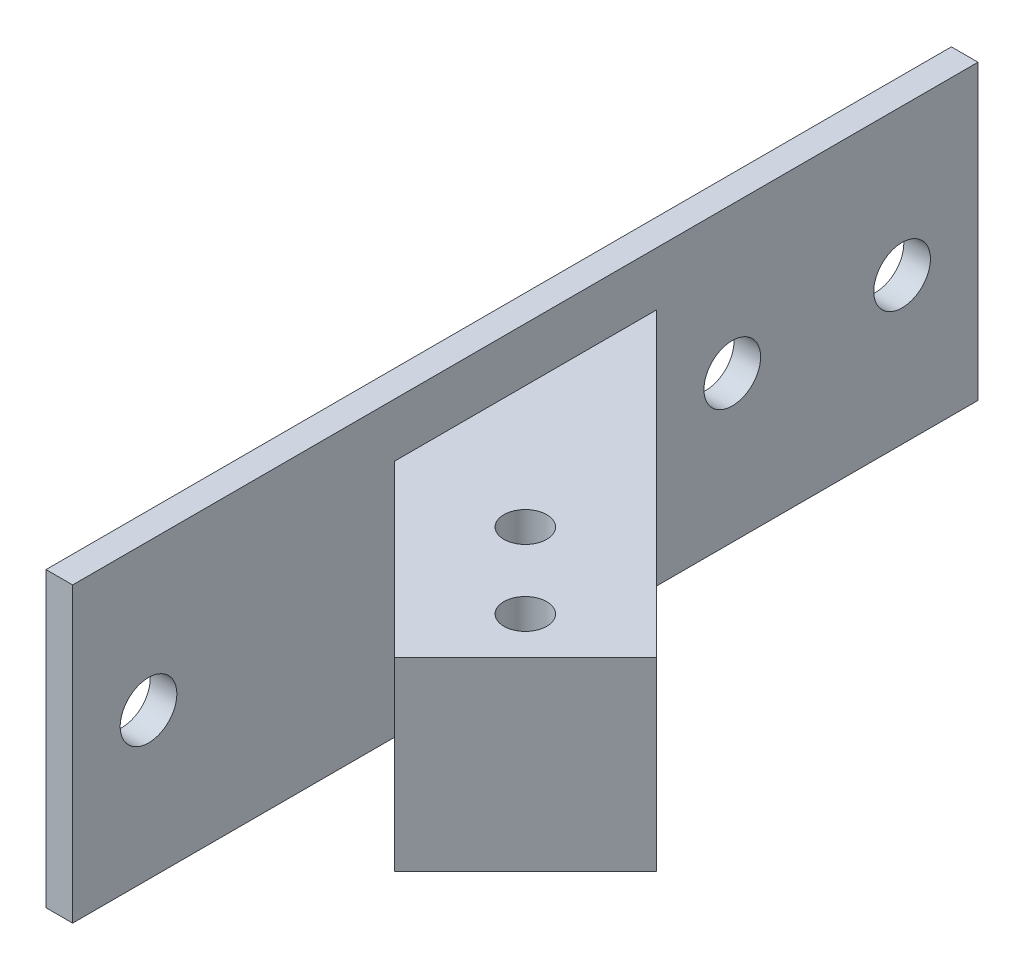
SolidWorks part; units mm, degrees
material "6061 Alloy"
ref_plane "Front" through (0, 0, 0) normal (0, 0, 1) x (1, 0, 0)
ref_plane "Top" through (0, 0, 0) normal (0, 1, 0) x (1, 0, 0)
ref_plane "Right" through (0, 0, 0) normal (1, 0, 0) x (0, 0, -1)
sketch "Sketch1" plane through (0, 0, 0) normal (1, 0, 0) x (0, 0, -1)
  line L1 (-53.975, 17.4625) -> (53.975, 17.4625)
  line L2 (-53.975, 17.4625) -> (-53.975, -17.4625)
  line L3 (-53.975, -17.4625) -> (53.975, -17.4625)
  line L4 (53.975, 17.4625) -> (53.975, -17.4625)
  line L5 (-53.975, 17.4625) -> (53.975, -17.4625) construction
  line L6 (-53.975, -17.4625) -> (53.975, 17.4625) construction
  point P0 (0, 0)
  dimension "D1" = 34.925
  dimension "D2" = 107.95
extrude "Boss-Extrude1" add sketch "Sketch1" along normal blind 3.175
sketch "Sketch3" plane through (0, 17.4625, 0) normal (0, 1, 0) x (1, 0, 0)
  line L0 (3.175, 0) -> (31.2383, -28.0633)
  line L1 (3.175, 53.975) -> (3.175, -53.975) construction
  line L2 (3.175, -20.2056) -> (21.1355, -38.1661)
  line L3 (3.175, 20.2056) -> (41.3411, -17.9605)
  line L4 (-3.9803, -13.0503) -> (21.1355, -38.1661) construction
  line L5 (16.2253, 7.1553) -> (41.3411, -17.9605) construction
  line L6 (6.1225, -2.9475) -> (31.2383, -28.0633) construction
  line L7 (21.1355, -38.1661) -> (31.2383, -28.0633)
  point P8 (21.1355, -17.9605)
  point P10 (28.5915, -25.4165)
  dimension "D1" = 14.2875
  dimension "D3" = 45
  dimension "D4" = 25.4
  dimension "D2" = 14.2875
sketch3d "3DSketch1"
  line L0 (3.175, 17.4625, 0) -> (31.2383, 17.4625, 28.0633) construction
sketch "Sketch4" plane through (29.6508, 0, 29.6508) normal (0.7071, 0, 0.7071) x (0.7071, 0, -0.7071)
  line L0 (2.2451, 17.4625) -> (2.2451, -17.4625) construction
  line L1 (-8.8039, -11.049) -> (13.2941, -11.049)
  line L2 (-8.8039, -11.049) -> (-8.8039, 11.049)
  line L3 (-8.8039, 11.049) -> (13.2941, 11.049)
  line L4 (13.2941, -11.049) -> (13.2941, 11.049)
  line L5 (-8.8039, -11.049) -> (13.2941, 11.049) construction
  line L6 (-8.8039, 11.049) -> (13.2941, -11.049) construction
  line L7 (40.4112, 17.4625) -> (-35.921, 17.4625) construction
  line L8 (-35.921, -17.4625) -> (40.4112, -17.4625) construction
  line L14 (-7.2164, 9.4615) -> (18.1836, -15.9385) construction
  line L15 (-10.4549, -12.7) -> (14.9451, 12.7) construction
  point P0 (2.2451, 0)
  point P12 (2.2451, 0)
  point P13 (2.2451, 0)
  dimension "D1" = 22.098
extrude "Boss-Extrude2" add sketch "Sketch4" against normal up to surface (28.6385 mm away) up to face at (3.175, 0, 0)
sketch "Sketch5" plane through (3.175, 0, 0) normal (1, 0, 0) x (0, 0, -1)
  line L0 (15.6256, 0) -> (24.6751, 0) construction
  line L1 (-53.975, 17.4625) -> (-53.975, -17.4625) construction
  line L2 (-44.9256, 0) -> (-53.975, 0) construction
  line L3 (-53.975, 0) -> (-35.8761, 0) construction
  line L4 (-35.8761, 11.049) -> (-35.8761, -11.049) construction
  line L5 (15.6256, 11.049) -> (15.6256, -11.049) construction
  line L6 (24.6751, 0) -> (44.9256, 0) construction
  line L7 (44.9256, 0) -> (53.975, 0) construction
  line L8 (53.975, -17.4625) -> (53.975, 17.4625) construction
  circle A0 centre (-44.9256, 0) radius 3.3782
  circle A1 centre (24.6751, 0) radius 3.3782
  circle A2 centre (44.9256, 0) radius 3.3782
  point P17 (-44.9256, 0)
  dimension "D2" = 6.7564
extrude "Cut-Extrude1" cut sketch "Sketch5" against normal up to next
sketch "Sketch6" plane through (0, 11.049, 0) normal (0, 1, 0) x (1, 0, 0)
  line L0 (31.2383, -28.0633) -> (26.7482, -23.5732) construction
  line L1 (39.0511, -20.2505) -> (23.4255, -35.8761) construction
  line L2 (31.2383, -28.0633) -> (17.7679, -14.5929) construction
  line L3 (23.4255, -35.8761) -> (5.465, -17.9156) construction
  line L4 (3.175, -15.6256) -> (23.4255, -35.8761) construction
  circle A0 centre (26.7482, -23.5732) radius 3.3782
  circle A1 centre (17.7679, -14.5929) radius 3.3782
  point P9 (23.4255, -35.8761)
  point P12 (5.465, -17.9156)
  dimension "D1" = 6.35
  dimension "D2" = 6.7564
  dimension "D3" = 25.4
  dimension "D4" = 19.05
hole_wizard "1/4-20 Tapped Hole1" positions "Sketch7" profile "Sketch8" tap size "1/4-20" standard "ANSI Inch" end condition through all
sketch "Sketch7" plane through (0, 11.049, 0) normal (0, 1, 0) x (1, 0, 0)
  point P0 (17.7679, -14.5929)
  point P3 (26.7482, -23.5732)
sketch "Sketch8" plane through (17.7679, 11.049, 14.5929) normal (1, 0, 0) x (0, 0, 1)
  line L0 (0, 0) -> (0, 28.5115)
  line L1 (0, 28.5115) -> (2.5527, 28.5115)
  line L2 (2.5527, 28.5115) -> (2.5527, 0)
  line L5 (2.5527, 0) -> (0, 0)
  line L11 (0, -6.35) -> (0, 107.95) construction
  dimension "Thru Tap Drill Dia." = 5.1054
  dimension "Thru Tap Drill Depth" = 28.5115
